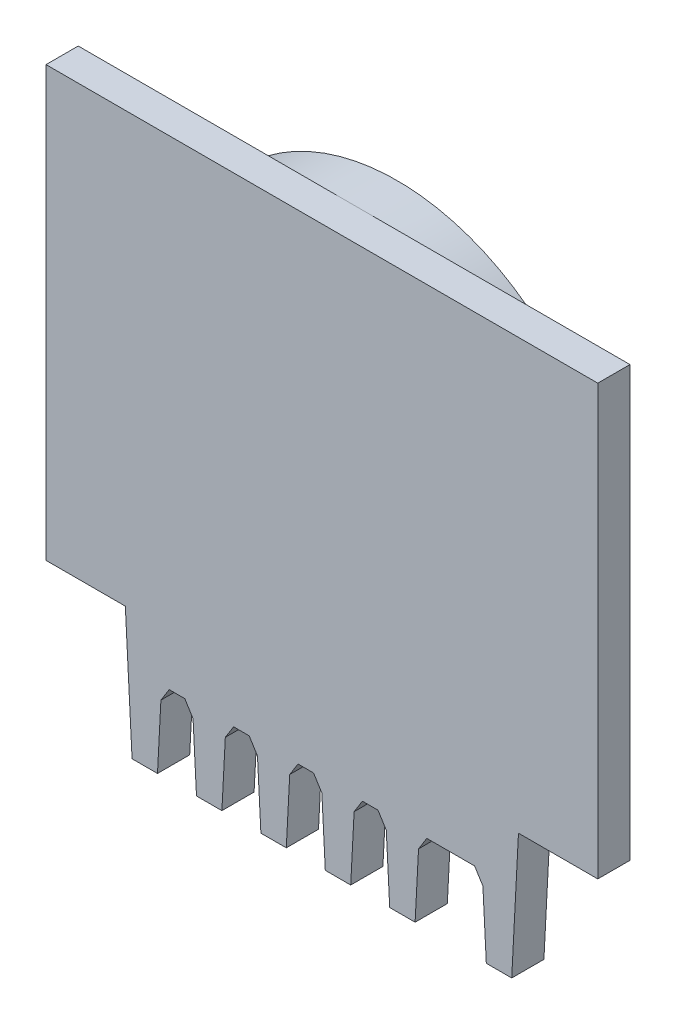
SolidWorks part; units mm, degrees
ref_plane "Front Plane" through (0, 0, 0) normal (0, 0, 1) x (1, 0, 0)
ref_plane "Top Plane" through (0, 0, 0) normal (0, 1, 0) x (1, 0, 0)
ref_plane "Right Plane" through (0, 0, 0) normal (1, 0, 0) x (0, 0, -1)
sketch "Sketch1" plane through (0, 0, 0) normal (0, 0, 1) x (1, 0, 0)
  line L0 (0, 0) -> (0, 26) construction
  line L1 (0, 26) -> (18.3124, 26) construction
  line L2 (18.3124, 26) -> (18.3124, 0) construction
  line L3 (18.3124, 0) -> (0, 0) construction
  line L4 (0, 3) -> (18.3124, 3) construction
  line L5 (0, 6) -> (18.3124, 6) construction
  line L6 (0.9062, 6) -> (0.9062, 0) construction
  line L7 (3.9062, 6) -> (3.9062, 0) construction
  line L8 (6.9062, 6) -> (6.9062, 0) construction
  line L9 (9.9062, 6) -> (9.9062, 0) construction
  line L10 (12.9062, 6) -> (12.9062, 0) construction
  line L11 (17.4062, 6) -> (17.4062, 0) construction
  line L12 (0.9062, 3) -> (3.9062, 3) construction
  line L13 (3.9062, 3) -> (6.9062, 3) construction
  line L14 (6.9062, 3) -> (9.9062, 3) construction
  line L15 (9.9062, 3) -> (12.9062, 3) construction
  line L16 (12.9062, 3) -> (17.4062, 3) construction
  line L17 (0.9062, 3) -> (0, 3) construction
  line L18 (17.4062, 3) -> (18.3124, 3) construction
  line L19 (2.4062, 3) -> (2.4062, 0) construction
  line L20 (5.4062, 3) -> (5.4062, 0) construction
  line L21 (8.4062, 3) -> (8.4062, 0) construction
  line L22 (11.4062, 3) -> (11.4062, 0) construction
  line L23 (15.1562, 3) -> (15.1562, 0) construction
  line L24 (14.4062, 3.75) -> (15.9062, 3.75) construction
  line L25 (0, 6) -> (0.3144, 0)
  line L26 (0.3144, 0) -> (1.4979, 0)
  line L27 (1.4979, 0) -> (1.6572, 3.0393)
  line L28 (3.1552, 3.0393) -> (3.3144, 0)
  line L29 (3.3144, 0) -> (4.4979, 0)
  line L30 (4.4979, 0) -> (4.6572, 3.0393)
  line L31 (6.1552, 3.0393) -> (6.3144, 0)
  line L32 (6.3144, 0) -> (7.4979, 0)
  line L33 (7.4979, 0) -> (7.6572, 3.0393)
  line L34 (9.1552, 3.0393) -> (9.3144, 0)
  line L35 (9.3144, 0) -> (10.4979, 0)
  line L36 (10.4979, 0) -> (10.6572, 3.0393)
  line L37 (12.1552, 3.0393) -> (12.3144, 0)
  line L38 (12.3144, 0) -> (13.4979, 0)
  line L39 (13.4979, 0) -> (13.6572, 3.0393)
  line L40 (16.6552, 3.0393) -> (16.8144, 0)
  line L41 (16.8144, 0) -> (17.9979, 0)
  line L42 (17.9979, 0) -> (18.3124, 6)
  line L44 (1.6572, 3.0393) -> (2.0426, 3.656)
  line L45 (0, 6) -> (-3.6938, 6)
  line L46 (-3.6938, 26) -> (22.0062, 26)
  line L47 (-3.6938, 6) -> (-3.6938, 26)
  line L48 (9.1562, 26) -> (9.1562, 6) construction
  line L49 (2.0426, 3.656) -> (2.7698, 3.656)
  line L50 (2.7698, 3.656) -> (3.1552, 3.0393)
  line L51 (4.6572, 3.0393) -> (5.0426, 3.656)
  line L52 (5.0426, 3.656) -> (5.7698, 3.656)
  line L53 (5.7698, 3.656) -> (6.1552, 3.0393)
  line L54 (7.6572, 3.0393) -> (8.0426, 3.656)
  line L55 (8.0426, 3.656) -> (8.7698, 3.656)
  line L56 (8.7698, 3.656) -> (9.1552, 3.0393)
  line L57 (10.6572, 3.0393) -> (11.0426, 3.656)
  line L58 (11.0426, 3.656) -> (11.7698, 3.656)
  line L59 (11.7698, 3.656) -> (12.1552, 3.0393)
  line L60 (13.6572, 3.0393) -> (14.0426, 3.656)
  line L61 (14.0426, 3.656) -> (16.2698, 3.656)
  line L62 (16.2698, 3.656) -> (16.6552, 3.0393)
  line L63 (18.3124, 6) -> (22.0062, 6)
  line L64 (22.0062, 6) -> (22.0062, 26)
  arc A0 (3.1552, 3.0393) -> (1.6572, 3.0393) centre (2.4062, 3) ccw construction
  arc A1 (6.1552, 3.0393) -> (4.6572, 3.0393) centre (5.4062, 3) ccw construction
  arc A2 (9.1552, 3.0393) -> (7.6572, 3.0393) centre (8.4062, 3) ccw construction
  arc A3 (12.1552, 3.0393) -> (10.6572, 3.0393) centre (11.4062, 3) ccw construction
  arc A4 (13.6572, 3.0393) -> (14.4062, 3.75) centre (14.4062, 3) cw construction
  arc A5 (16.6552, 3.0393) -> (15.9062, 3.75) centre (15.9062, 3) ccw construction
  circle A7 centre (9.1562, 16) radius 10 construction
  dimension "D7" = 0.75
  dimension "D11" = 20
  dimension "D1" = 3
  dimension "D2" = 6
  dimension "D4" = 3
  dimension "D5" = 25.7
  dimension "D6" = 4.5
  dimension "D8" = 3
  dimension "D9" = 18.3124
  dimension "D10" = 26
extrude "Boss-Extrude1" add sketch "Sketch1" along normal blind 1.5
sketch "Sketch3" plane through (0, 0, 0) normal (0, 0, 1) x (1, 0, 0)
  line L0 (-0.4005, 6) -> (18.7129, 6)
  line L1 (18.7129, 3) -> (-0.4005, 3) construction
  line L2 (-0.4005, 0) -> (18.7129, 0) construction
  line L3 (-0.4005, -0.5) -> (18.7129, -0.5) construction
  line L4 (18.7129, -0.5) -> (18.7129, 6) construction
  line L5 (-0.4005, 6) -> (-0.4005, -0.5) construction
  line L6 (18.3124, 0) -> (0, 0) construction
  line L7 (0, 3) -> (18.3124, 3) construction
  line L8 (0, 6) -> (18.3124, 6) construction
  line L9 (0.3407, -0.5) -> (0, 6) construction
  line L10 (18.3124, 6) -> (17.9717, -0.5) construction
  line L11 (17.9979, 0) -> (18.3124, 6) construction
  line L12 (0, 6) -> (0.3144, 0) construction
  line L13 (5.4062, 6) -> (5.4062, -0.5) construction
  line L14 (3.9062, 6) -> (3.9062, -0.5) construction
  line L15 (5.4062, 3) -> (5.4062, 0) construction
  line L16 (3.1572, 3) -> (3.3407, -0.5) construction
  line L17 (2.7567, 3) -> (2.9401, -0.5)
  line L18 (3.1552, 3.0393) -> (3.3144, 0) construction
  line L19 (2.9401, -0.5) -> (4.8723, -0.5)
  line L20 (4.8723, -0.5) -> (5.0557, 3)
  line L21 (2.8484, 1.25) -> (3.2478, 1.2709) construction
  line L22 (5.9401, -0.5) -> (5.7567, 3)
  line L26 (7.8723, -0.5) -> (5.9401, -0.5)
  line L27 (8.0557, 3) -> (7.8723, -0.5)
  line L30 (2.4062, -0.5) -> (2.4062, 6) construction
  line L31 (2.4062, 3) -> (2.4062, 0) construction
  line L32 (8.4062, 6) -> (8.4062, -0.5) construction
  line L34 (11.4062, -0.5) -> (11.4062, 6) construction
  line L35 (15.1562, -0.5) -> (15.1562, 6) construction
  line L36 (8.4062, 3) -> (8.4062, 0) construction
  line L37 (11.4062, 3) -> (11.4062, 0) construction
  line L38 (15.1562, 3) -> (15.1562, 0) construction
  line L39 (10.8723, -0.5) -> (11.0557, 3)
  line L40 (8.9401, -0.5) -> (10.8723, -0.5)
  line L41 (8.7567, 3) -> (8.9401, -0.5)
  line L42 (11.9401, -0.5) -> (11.7567, 3)
  line L43 (13.8723, -0.5) -> (11.9401, -0.5)
  line L44 (14.0557, 3) -> (13.8723, -0.5)
  line L45 (16.4401, -0.5) -> (18.3723, -0.5)
  line L46 (16.2567, 3) -> (16.4401, -0.5)
  line L47 (18.3723, -0.5) -> (18.7129, 6)
  line L48 (1.8723, -0.5) -> (-0.0599, -0.5)
  line L49 (2.0557, 3) -> (1.8723, -0.5)
  line L50 (-0.0599, -0.5) -> (-0.4005, 6)
  line L51 (16.2567, 3) -> (14.0557, 3)
  line L52 (11.7567, 3) -> (11.0557, 3)
  line L53 (8.7567, 3) -> (8.0557, 3)
  line L54 (5.7567, 3) -> (5.0557, 3)
  line L55 (2.7567, 3) -> (2.0557, 3)
  dimension "D1" = 0.5
  dimension "D2" = 0.4
ref_plane "Plane1" through (3.9062, 0, 0) normal (1, 0, 0) x (0, 0, -1)
sketch "Sketch4" plane through (3.9062, 0, 0) normal (1, 0, 0) x (0, 0, -1)
  line L0 (0, 6) -> (0, -0.5) construction
  line L1 (0.6, 6) -> (-2.1, 6) construction
  line L2 (0.6, 6) -> (0.6, -0.5) construction
  line L3 (0.6, -0.5) -> (-2.1, -0.5) construction
  line L4 (-2.1, 6) -> (-2.1, -0.5) construction
  line L5 (-0.75, -0.5) -> (-0.75, 6) construction
  line L6 (-1.5, 6) -> (-1.5, -0.5) construction
  line L7 (0.6, 2.4005) -> (-2.1, 2.4005) construction
  line L8 (0.3, 6) -> (0.3, -0.5) construction
  line L9 (0.6, 2.4005) -> (3.846, 6) construction
  line L10 (2.2302, 6) -> (0.6, 4.1923) construction
  line L11 (0.6, 4.1923) -> (1.7139, 3.1878) construction
  line L12 (1.7139, 3.1878) -> (4.25, 6)
  line L13 (4.25, 6) -> (0.6, 6) construction
  line L14 (0.3, 1) -> (-1.8, 1) construction
  line L15 (-2.1, 0) -> (0.6, 0) construction
  line L16 (1.7139, 3.1878) -> (1.4912, 3.3887)
  line L17 (1.4912, 3.3887) -> (0.6, 2.4005)
  line L18 (-3.2139, 3.1878) -> (-5.75, 6)
  line L19 (-3.2139, 3.1878) -> (-2.9912, 3.3887)
  line L20 (-2.9912, 3.3887) -> (-2.1, 2.4005)
  line L21 (-2.1, 6) -> (-5.75, 6) construction
  line L22 (0.6, 3.0724) -> (3.2401, 6) construction
  arc A0 (0.4965, 2.2224) -> (0.6, -0.5) centre (4.2, 1) ccw
  arc A1 (0.6, 2.4005) -> (0.4965, 2.2224) centre (0.9713, 2.0656) ccw
  arc A2 (-2.1, 2.4005) -> (-1.9965, 2.2224) centre (-2.4713, 2.0656) cw
  arc A3 (-1.9965, 2.2224) -> (-2.1, -0.5) centre (-5.7, 1) cw
  dimension "D6" = 0.5
  dimension "D1" = 0.6
  dimension "D2" = 0.3
  dimension "D3" = 1.5
  dimension "D4" = 1
  dimension "D5" = 0.3
  dimension "D7" = 10
sketch "Sketch5" plane through (0, 0, 0) normal (1, 0, 0) x (0, 0, -1)
  line L0 (2.2302, 6) -> (0.6, 4.1923) construction
  line L1 (0.6, 4.1923) -> (1.7139, 3.1878) construction
  line L2 (1.7139, 3.1878) -> (4.25, 6) construction
  line L3 (2.2302, 6) -> (0.6, 4.1923) construction
  line L4 (0.6, 4.1923) -> (1.7139, 3.1878) construction
  line L5 (1.7139, 3.1878) -> (4.25, 6) construction
ref_plane "Plane2" through (0, 2.6105, -2.3541) normal (0, 0.7426, -0.6697) x (1, 0, 0)
sketch "Sketch6" plane through (0, 2.6105, -2.3541) normal (0, 0.7426, -0.6697) x (1, 0, 0)
  line L1 (3.9062, -2.362) -> (3.9062, -0.862) construction
  line L2 (3.9062, -2.362) -> (3.9062, -5.0612) construction
  line L3 (4.6562, -5.0612) -> (3.1562, -5.0612)
  line L4 (4.6562, -1.612) -> (3.1562, -1.612) construction
  line L5 (3.1562, -1.612) -> (3.1562, -5.0612)
  line L6 (4.6562, -1.612) -> (4.6562, -5.0612)
  line L10 (2.4062, -5.0612) -> (15.1562, -5.0612) construction
  line L11 (15.1562, -5.0612) -> (15.1562, -0.862) construction
  line L12 (15.1562, -0.862) -> (2.4062, -0.862) construction
  line L13 (2.4062, -0.862) -> (2.4062, -5.0612) construction
  line L14 (15.1562, 0.3349) -> (15.1562, -4.0182) construction
  line L15 (2.4062, 0.3349) -> (2.4062, -4.0182) construction
  line L16 (11.4062, -5.0612) -> (11.4062, -0.862) construction
  line L17 (8.4062, -5.0612) -> (8.4062, -0.862) construction
  line L18 (5.4062, -5.0612) -> (5.4062, -0.862) construction
  line L19 (5.4062, -4.0182) -> (5.4062, 0.3349) construction
  line L20 (8.4062, -4.0182) -> (8.4062, 0.3349) construction
  line L21 (11.4062, 0.3349) -> (11.4062, -4.0182) construction
  line L22 (0.1562, -1.612) -> (0.1562, -5.0612)
  line L23 (0.1562, -5.0612) -> (1.6562, -5.0612)
  line L24 (1.6562, -1.612) -> (1.6562, -5.0612)
  line L25 (7.6562, -1.612) -> (7.6562, -5.0612)
  line L26 (6.1562, -5.0612) -> (7.6562, -5.0612)
  line L27 (6.1562, -1.612) -> (6.1562, -5.0612)
  line L28 (10.6562, -1.612) -> (10.6562, -5.0612)
  line L29 (10.6562, -5.0612) -> (9.1562, -5.0612)
  line L30 (9.1562, -1.612) -> (9.1562, -5.0612)
  line L31 (13.6562, -1.612) -> (13.6562, -5.0612)
  line L32 (12.1562, -5.0612) -> (13.6562, -5.0612)
  line L33 (12.1562, -1.612) -> (12.1562, -5.0612)
  line L34 (18.1562, -1.612) -> (18.1562, -5.0612)
  line L35 (18.1562, -5.0612) -> (16.6562, -5.0612)
  line L36 (16.6562, -1.612) -> (16.6562, -5.0612)
  circle A0 centre (3.9062, -1.612) radius 0.75 construction
  arc A1 (4.6562, -1.612) -> (3.1562, -1.612) centre (3.9062, -1.612) ccw
  arc A2 (0.1562, -1.612) -> (1.6562, -1.612) centre (0.9062, -1.612) cw
  arc A3 (6.1562, -1.612) -> (7.6562, -1.612) centre (6.9062, -1.612) cw
  arc A4 (10.6562, -1.612) -> (9.1562, -1.612) centre (9.9062, -1.612) ccw
  arc A5 (12.1562, -1.612) -> (13.6562, -1.612) centre (12.9062, -1.612) cw
  arc A6 (18.1562, -1.612) -> (16.6562, -1.612) centre (17.4062, -1.612) ccw
ref_plane "Plane3" through (0, 1.6223, -1.463) normal (0, 0.7426, -0.6697) x (1, 0, 0)
sketch "Sketch7" plane through (0, 1.6223, -1.463) normal (0, 0.7426, -0.6697) x (1, 0, 0)
  line L0 (3.1562, -1.612) -> (3.1562, -5.0612) construction
  line L1 (4.6562, -5.0612) -> (3.1562, -5.0612) construction
  line L2 (4.6562, -1.612) -> (4.6562, -5.0612) construction
  line L3 (3.1562, -1.612) -> (3.1562, -5.0612) construction
  line L4 (4.6562, -5.0612) -> (3.1562, -5.0612) construction
  line L5 (4.6562, -1.612) -> (4.6562, -5.0612) construction
  line L6 (3.9062, -0.862) -> (3.9062, -5.0612) construction
  line L7 (4.6562, -1.612) -> (3.1562, -1.612) construction
  line L8 (4.6562, -2.362) -> (3.1562, -2.362) construction
  line L9 (3.4562, -1.612) -> (3.4562, -2.362)
  line L10 (3.4562, -2.362) -> (4.3562, -2.362)
  line L11 (4.3562, -2.362) -> (4.3562, -1.612)
  line L12 (2.4062, -0.862) -> (2.4062, -5.0612) construction
  line L13 (2.4062, -5.0612) -> (15.1562, -5.0612) construction
  line L14 (15.1562, -0.862) -> (2.4062, -0.862) construction
  line L15 (5.4062, -5.0612) -> (5.4062, -0.862) construction
  line L16 (8.4062, -5.0612) -> (8.4062, -0.862) construction
  line L17 (11.4062, -5.0612) -> (11.4062, -0.862) construction
  line L18 (15.1562, -5.0612) -> (15.1562, -0.862) construction
  line L19 (2.4062, -0.862) -> (2.4062, -5.0612) construction
  line L20 (2.4062, -5.0612) -> (15.1562, -5.0612) construction
  line L21 (15.1562, -0.862) -> (2.4062, -0.862) construction
  line L22 (5.4062, -5.0612) -> (5.4062, -0.862) construction
  line L23 (8.4062, -5.0612) -> (8.4062, -0.862) construction
  line L24 (11.4062, -5.0612) -> (11.4062, -0.862) construction
  line L25 (15.1562, -5.0612) -> (15.1562, -0.862) construction
  line L26 (0.4562, -2.362) -> (0.4562, -1.612)
  line L27 (1.3562, -2.362) -> (0.4562, -2.362)
  line L28 (1.3562, -1.612) -> (1.3562, -2.362)
  line L29 (7.3562, -2.362) -> (6.4562, -2.362)
  line L30 (7.3562, -1.612) -> (7.3562, -2.362)
  line L31 (6.4562, -2.362) -> (6.4562, -1.612)
  line L32 (9.4562, -1.612) -> (9.4562, -2.362)
  line L33 (10.3562, -2.362) -> (10.3562, -1.612)
  line L34 (9.4562, -2.362) -> (10.3562, -2.362)
  line L35 (13.3562, -1.612) -> (13.3562, -2.362)
  line L36 (12.4562, -2.362) -> (12.4562, -1.612)
  line L37 (13.3562, -2.362) -> (12.4562, -2.362)
  line L38 (16.9562, -1.612) -> (16.9562, -2.362)
  line L39 (17.8562, -2.362) -> (17.8562, -1.612)
  line L40 (16.9562, -2.362) -> (17.8562, -2.362)
  arc A0 (4.6562, -1.612) -> (3.1562, -1.612) centre (3.9062, -1.612) ccw construction
  arc A1 (4.6562, -1.612) -> (3.1562, -1.612) centre (3.9062, -1.612) ccw construction
  circle A2 centre (3.9062, -1.612) radius 0.45 construction
  arc A3 (4.3562, -1.612) -> (3.4562, -1.612) centre (3.9062, -1.612) ccw
  arc A4 (0.4562, -1.612) -> (1.3562, -1.612) centre (0.9062, -1.612) cw
  arc A5 (6.4562, -1.612) -> (7.3562, -1.612) centre (6.9062, -1.612) cw
  arc A6 (10.3562, -1.612) -> (9.4562, -1.612) centre (9.9062, -1.612) ccw
  arc A7 (12.4562, -1.612) -> (13.3562, -1.612) centre (12.9062, -1.612) cw
  arc A8 (17.8562, -1.612) -> (16.9562, -1.612) centre (17.4062, -1.612) ccw
ref_plane "bisect" through (0, 0, 0.75) normal (0, 0, 1) x (1, 0, 0)
ref_plane "insert_surface" through (0, 6, 0) normal (0, 1, 0) x (1, 0, 0)
sketch "Sketch8" plane through (0, 6, 0) normal (0, 1, 0) x (1, 0, 0)
  line L0 (18.7129, -0.75) -> (-0.4005, -0.75) construction
  line L1 (-0.4005, 0.6) -> (18.7129, 0.6)
  line L2 (-0.4005, 0.6) -> (-0.4005, -2.1)
  line L3 (-0.4005, -2.1) -> (18.7129, -2.1)
  line L4 (18.7129, 0.6) -> (18.7129, -2.1)
  line L5 (9.1562, 0.6) -> (9.1562, -2.1) construction
  line L6 (0, 0) -> (18.3124, 0) construction
  line L7 (0, 0) -> (0, -1.5) construction
  line L8 (0, -1.5) -> (18.3124, -1.5) construction
  line L9 (18.3124, 0) -> (18.3124, -1.5) construction
  line L10 (18.7129, 0.3) -> (-0.4005, 0.3) construction
  line L11 (18.7129, -1.8) -> (-0.4005, -1.8) construction
sketch "Sketch9" plane through (0, 0, 0) normal (0, 0, 1) x (1, 0, 0)
  line L0 (18.3723, -0.5) -> (18.7129, 6) construction
  line L1 (-0.4005, 6) -> (18.7129, 6) construction
  line L2 (-0.0599, -0.5) -> (-0.4005, 6) construction
  line L3 (1.8723, -0.5) -> (-0.0599, -0.5) construction
  line L4 (2.0557, 3) -> (1.8723, -0.5) construction
  line L5 (2.7567, 3) -> (2.0557, 3) construction
  line L6 (2.7567, 3) -> (2.9401, -0.5) construction
  line L7 (2.9401, -0.5) -> (4.8723, -0.5) construction
  line L8 (4.8723, -0.5) -> (5.0557, 3) construction
  line L9 (5.7567, 3) -> (5.0557, 3) construction
  line L10 (5.9401, -0.5) -> (5.7567, 3) construction
  line L11 (7.8723, -0.5) -> (5.9401, -0.5) construction
  line L12 (8.0557, 3) -> (7.8723, -0.5) construction
  line L13 (8.7567, 3) -> (8.0557, 3) construction
  line L14 (8.7567, 3) -> (8.9401, -0.5) construction
  line L15 (8.9401, -0.5) -> (10.8723, -0.5) construction
  line L16 (10.8723, -0.5) -> (11.0557, 3) construction
  line L17 (11.7567, 3) -> (11.0557, 3) construction
  line L18 (11.9401, -0.5) -> (11.7567, 3) construction
  line L19 (13.8723, -0.5) -> (11.9401, -0.5) construction
  line L20 (14.0557, 3) -> (13.8723, -0.5) construction
  line L21 (16.2567, 3) -> (14.0557, 3) construction
  line L22 (16.2567, 3) -> (16.4401, -0.5) construction
  line L23 (16.4401, -0.5) -> (18.3723, -0.5) construction
  line L24 (18.3723, -0.5) -> (18.7129, 6)
  line L25 (-0.4005, 6) -> (18.7129, 6) construction
  line L26 (-0.0599, -0.5) -> (-0.4005, 6)
  line L27 (1.8723, -0.5) -> (-0.0599, -0.5)
  line L28 (2.0557, 3) -> (1.8723, -0.5)
  line L29 (2.7567, 3) -> (2.0557, 3) construction
  line L30 (2.7567, 3) -> (2.9401, -0.5)
  line L31 (2.9401, -0.5) -> (4.8723, -0.5)
  line L32 (4.8723, -0.5) -> (5.0557, 3)
  line L33 (5.7567, 3) -> (5.0557, 3) construction
  line L34 (5.9401, -0.5) -> (5.7567, 3)
  line L35 (7.8723, -0.5) -> (5.9401, -0.5)
  line L36 (8.0557, 3) -> (7.8723, -0.5)
  line L37 (8.7567, 3) -> (8.0557, 3) construction
  line L38 (8.7567, 3) -> (8.9401, -0.5)
  line L39 (8.9401, -0.5) -> (10.8723, -0.5)
  line L40 (10.8723, -0.5) -> (11.0557, 3)
  line L41 (11.7567, 3) -> (11.0557, 3) construction
  line L42 (11.9401, -0.5) -> (11.7567, 3)
  line L43 (13.8723, -0.5) -> (11.9401, -0.5)
  line L44 (14.0557, 3) -> (13.8723, -0.5)
  line L45 (16.2567, 3) -> (14.0557, 3) construction
  line L46 (16.2567, 3) -> (16.4401, -0.5)
  line L47 (16.4401, -0.5) -> (18.3723, -0.5)
  line L48 (16.2567, 3) -> (16.2567, 6)
  line L49 (14.0557, 3) -> (14.0557, 6)
  line L50 (11.7567, 3) -> (11.7567, 6)
  line L51 (18.7129, 6) -> (-0.4005, 6) construction
  line L52 (11.0557, 3) -> (11.0557, 6)
  line L53 (-0.4005, 6) -> (18.7129, 6) construction
  line L54 (8.7567, 3) -> (8.7567, 6)
  line L55 (8.0557, 3) -> (8.0557, 6)
  line L58 (5.7567, 3) -> (5.7567, 6)
  line L60 (5.0557, 3) -> (5.0557, 6)
  line L62 (15.1562, -0.5) -> (15.1562, 6) construction
  line L63 (15.1562, -0.5) -> (15.1562, 6) construction
  line L64 (2.7567, 3) -> (2.7567, 6)
  line L65 (2.0557, 3) -> (2.0557, 6)
  line L67 (18.7129, 6) -> (16.2567, 6)
  line L68 (14.0557, 6) -> (11.7567, 6)
  line L69 (11.0557, 6) -> (8.7567, 6)
  line L70 (8.0557, 6) -> (5.7567, 6)
  line L71 (5.0557, 6) -> (2.7567, 6)
  line L72 (2.0557, 6) -> (-0.4005, 6)
sketch "Sketch10" plane through (0, 0, 0) normal (0, 0, 1) x (1, 0, 0)
  circle A0 centre (9.1562, 16) radius 10
extrude "Boss-Extrude2" add sketch "Sketch10" against normal blind 2
sketch "Sketch11" plane through (0, 6, 0) normal (0, 1, 0) x (1, 0, 0)
  line L0 (9.1562, -0.75) -> (9.1562, -5.75) construction
  line L1 (-0.8438, 4.25) -> (19.1562, 4.25)
  line L2 (-0.8438, 4.25) -> (-0.8438, -5.75)
  line L3 (-0.8438, -5.75) -> (19.1562, -5.75)
  line L4 (19.1562, 4.25) -> (19.1562, -5.75)
  line L5 (9.1562, -0.75) -> (9.1562, 4.25) construction
  line L6 (9.1562, -0.75) -> (19.1562, -0.75) construction
  line L7 (9.1562, -0.75) -> (-0.8438, -0.75) construction
  line L8 (-10.5124, -0.75) -> (10.5124, -0.75) construction
  dimension "D1" = 10
  dimension "D2" = 20
